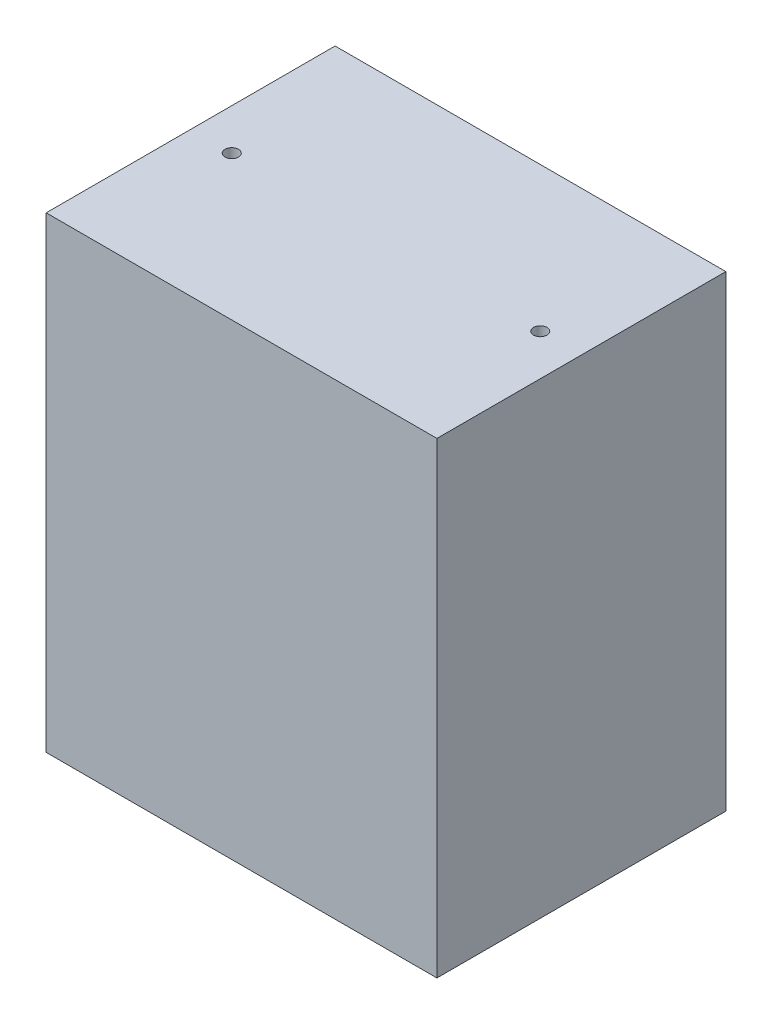
SolidWorks part; units mm, degrees
ref_plane "Front Plane" through (0, 0, 0) normal (0, 0, 1) x (1, 0, 0)
ref_plane "Top Plane" through (0, 0, 0) normal (0, 1, 0) x (1, 0, 0)
ref_plane "Right Plane" through (0, 0, 0) normal (1, 0, 0) x (0, 0, -1)
sketch "Sketch1" plane through (0, 0, 0) normal (0, 0, 1) x (1, 0, 0)
  line L5 (-40.5723, 48.5221) -> (40.5723, 48.5221)
  line L6 (-40.5723, 48.5221) -> (-40.5723, -48.5221)
  line L7 (-40.5723, -48.5221) -> (40.5723, -48.5221)
  line L8 (40.5723, 48.5221) -> (40.5723, -48.5221)
  circle A0 centre (0, 0) radius 37.475
  point P0 (0, 0)
  dimension "D3" = 74.95
  dimension "D1" = 97.0441
  dimension "D2" = 81.1447
extrude "Boss-Extrude1" add sketch "Sketch1" along normal blind 60 contours L5 L8 L7 L6
sketch "Sketch2" plane through (0, 48.5221, 0) normal (0, 1, 0) x (1, 0, 0)
  line L0 (0, 0) -> (0, -60) construction
  line L1 (-40.5723, 0) -> (40.5723, 0) construction
  line L2 (-40.5723, -60) -> (40.5723, -60) construction
  line L3 (-40.5723, -30) -> (40.5723, -30) construction
  line L4 (-40.5723, -60) -> (-40.5723, 0) construction
  line L5 (40.5723, -60) -> (40.5723, 0) construction
  circle A0 centre (-32.0323, -30) radius 1.4
  circle A1 centre (32.032, -30) radius 1.4
  point P16 (0, 0)
  dimension "D1" = 8.54
  dimension "D2" = 2.8
  dimension "D3" = 8.5403
extrude "Cut-Extrude1" cut sketch "Sketch2" against normal blind 20
sketch "Sketch3" plane through (0, 0, 60) normal (0, 0, 1) x (1, 0, 0)
  line L0 (0, 4.9375) -> (0, -4.9375) construction
  circle A0 centre (0, 0) radius 4.9375
  dimension "D1" = 9.875
